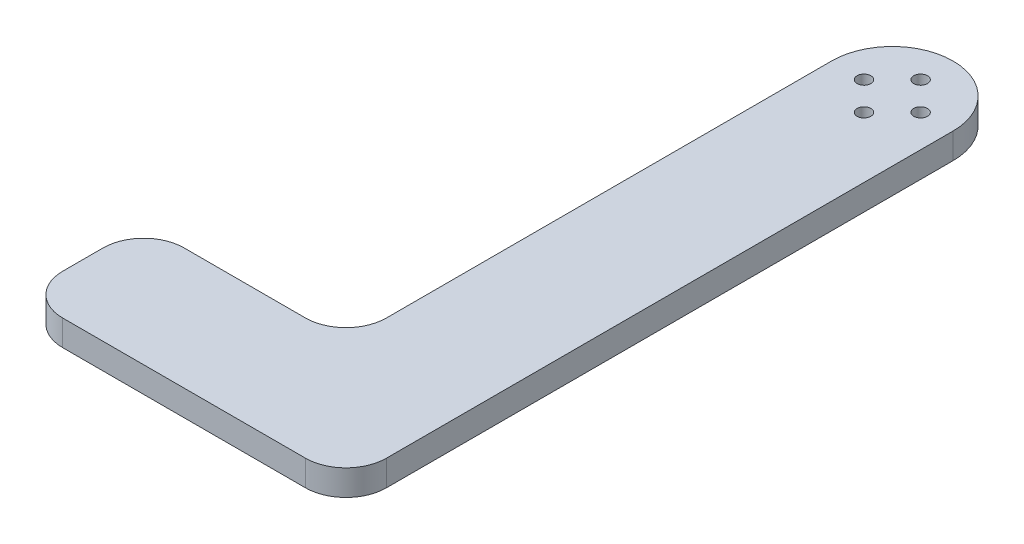
SolidWorks part; units mm, degrees
material "Pine"
ref_plane "Front Plane" through (0, 0, 0) normal (0, 0, 1) x (1, 0, 0)
ref_plane "Top Plane" through (0, 0, 0) normal (0, 1, 0) x (1, 0, 0)
ref_plane "Right Plane" through (0, 0, 0) normal (1, 0, 0) x (0, 0, -1)
sketch "Sketch2" plane through (0, 0, 0) normal (0, 1, 0) x (1, 0, 0)
  line L0 (-15, 0) -> (-15, -120)
  line L1 (-15, -120) -> (-65, -120)
  line L2 (-65, -120) -> (-65, -150)
  line L3 (-65, -150) -> (15, -150)
  line L4 (15, -150) -> (15, 0)
  circle A0 centre (0, 0) radius 15
  circle A1 centre (0, 0) radius 7 construction
  dimension "D1" = 30
  dimension "D2" = 14
  dimension "D3" = 30
  dimension "D4" = 50
  dimension "D5" = 150
extrude "Boss-Extrude1" add sketch "Sketch2" along normal blind 6.35 contours A0 L0 L1 L2 L3 L4 | A0 region at (-10.6259, 0, 95.2348) region at (0, 0, 0)
sketch "Sketch3" plane through (0, 6.35, 0) normal (0, 1, 0) x (1, 0, 0)
  circle A0 centre (0, 0) radius 7 construction
  circle A1 centre (0, 0) radius 7 construction
  point P3 (0, 7)
hole_wizard "M3 Clearance Hole1" positions "Sketch3" profile "Sketch4" hole size "M3" standard "ANSI Metric" end condition through all
sketch "Sketch4" plane through (0, 6.35, -7) normal (1, 0, 0) x (0, 0, 1)
  line L0 (0, 0) -> (0, 6.35)
  line L1 (0, 6.35) -> (1.7, 6.35)
  line L2 (1.7, 6.35) -> (1.7, 0)
  line L5 (1.7, 0) -> (0, 0)
  line L11 (0, -6.35) -> (0, 107.95) construction
  dimension "Thru Hole Dia." = 3.4
  dimension "Thru Hole Depth" = 6.35
pattern_circular "CirPattern1" count 4 over 360 about axis through (0, 6.35, 0) along (0, -1, 0) of "M3 Clearance Hole1" reverse direction yes
fillet "Fillet1" radius 10 4 edges at (15, 3.175, 150) (-65, 3.175, 150) (-65, 3.175, 120) (-15, 3.175, 120)
